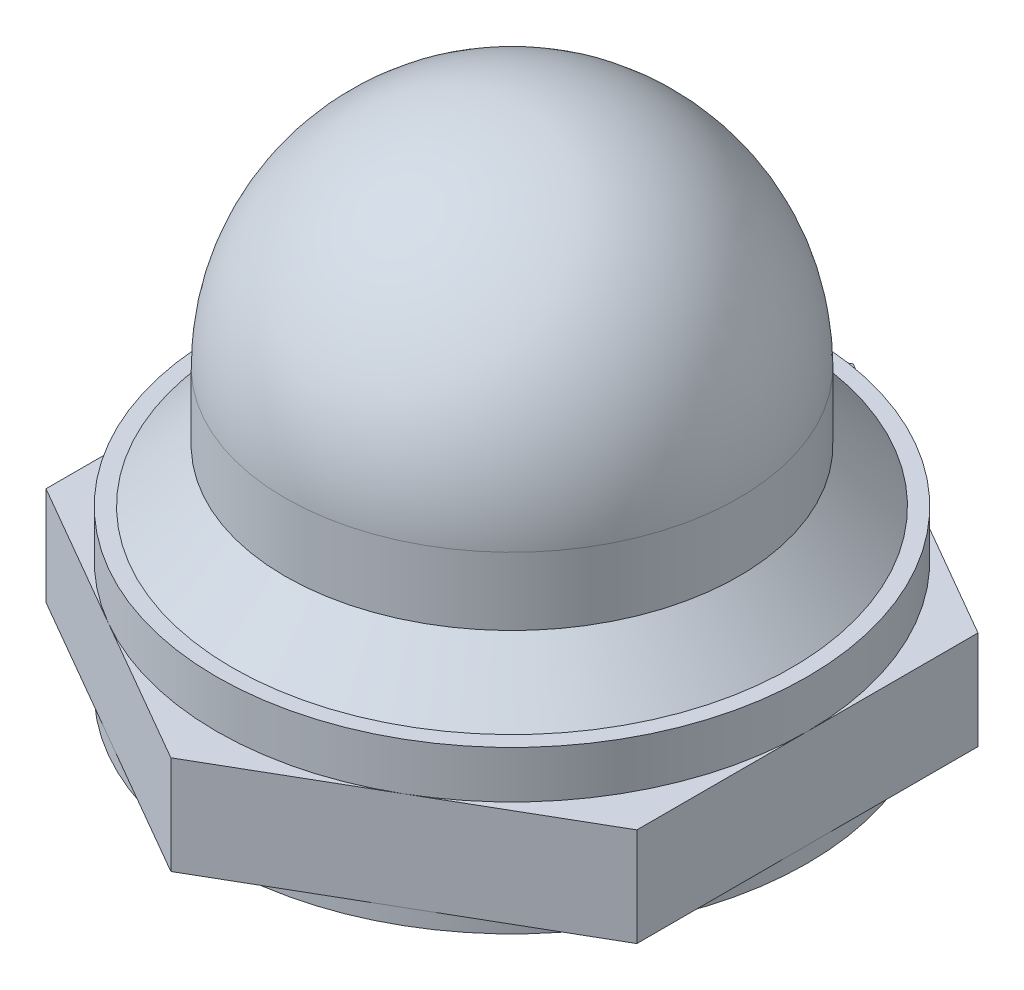
SolidWorks part; units mm, degrees
material "Silicon Rubber"
ref_plane "Front Plane" through (0, 0, 0) normal (0, 0, 1) x (1, 0, 0)
ref_plane "Top Plane" through (0, 0, 0) normal (0, 1, 0) x (1, 0, 0)
ref_plane "Right Plane" through (0, 0, 0) normal (1, 0, 0) x (0, 0, -1)
sketch "Sketch1" plane through (0, 0, 0) normal (0, 1, 0) x (1, 0, 0)
  line L1 (4.7625, 2.7496) -> (0, 5.4993)
  line L2 (0, 5.4993) -> (-4.7625, 2.7496)
  line L3 (-4.7625, 2.7496) -> (-4.7625, -2.7496)
  line L4 (-4.7625, -2.7496) -> (0, -5.4993)
  line L5 (0, -5.4993) -> (4.7625, -2.7496)
  line L6 (4.7625, -2.7496) -> (4.7625, 2.7496)
  circle A0 centre (0, 0) radius 4.7625 construction
  circle A1 centre (0, 0) radius 3.175
  point P1 (4.7625, 0)
  dimension "D2" = 6.35
  dimension "D1" = 9.525
extrude "Boss-Extrude1" add sketch "Sketch1" along normal blind 1.5875
sketch "Sketch2" plane through (0, 0, 0) normal (1, 0, 0) x (0, 0, -1)
  line L0 (0, 0) -> (0, 7.9502) construction
  line L1 (-2.7496, 0) -> (2.7496, 0) construction
  line L2 (2.3876, 0) -> (2.3876, 4.2926) construction
  line L3 (3.6576, 3.2004) -> (3.6576, 4.2926)
  line L4 (3.6576, 3.2004) -> (4.5085, 2.3495)
  line L5 (4.5085, 2.3495) -> (4.7625, 2.3495)
  line L6 (4.7625, 2.3495) -> (4.7625, 1.5875)
  line L7 (4.7625, 1.5875) -> (3.175, 1.5875)
  line L8 (3.175, 1.5875) -> (3.175, 4.2926)
  line L9 (3.6576, 0) -> (3.6576, 4.2926) construction
  line L10 (2.7496, 1.5875) -> (5.4993, 1.5875) construction
  line L11 (3.175, 0) -> (3.175, 4.2926) construction
  line L12 (4.7625, 0) -> (-4.7625, 0) construction
  line L13 (2.7496, 0) -> (5.4993, 0) construction
  line L14 (3.175, 0) -> (4.7625, 0)
  line L15 (4.7625, 0) -> (4.7625, -0.254)
  line L16 (3.175, 0) -> (4.7625, 0) construction
  line L17 (0, 7.9502) -> (0, 7.4676)
  line L18 (4.7625, -0.254) -> (3.175, -0.254)
  line L19 (3.175, -0.254) -> (3.175, 0)
  arc A0 (3.6576, 4.2926) -> (0, 7.9502) centre (0, 4.2926) ccw
  arc A1 (3.175, 4.2926) -> (0, 7.4676) centre (0, 4.2926) ccw
  dimension "D4" = 0.4826
  dimension "D1" = 7.9502
  dimension "D2" = 2.3876
  dimension "D5" = 45
  dimension "D6" = 0.762
  dimension "D7" = 0.254
  dimension "D8" = 0.254
revolve "Revolve1" add sketch "Sketch2" angle 360 about L0
